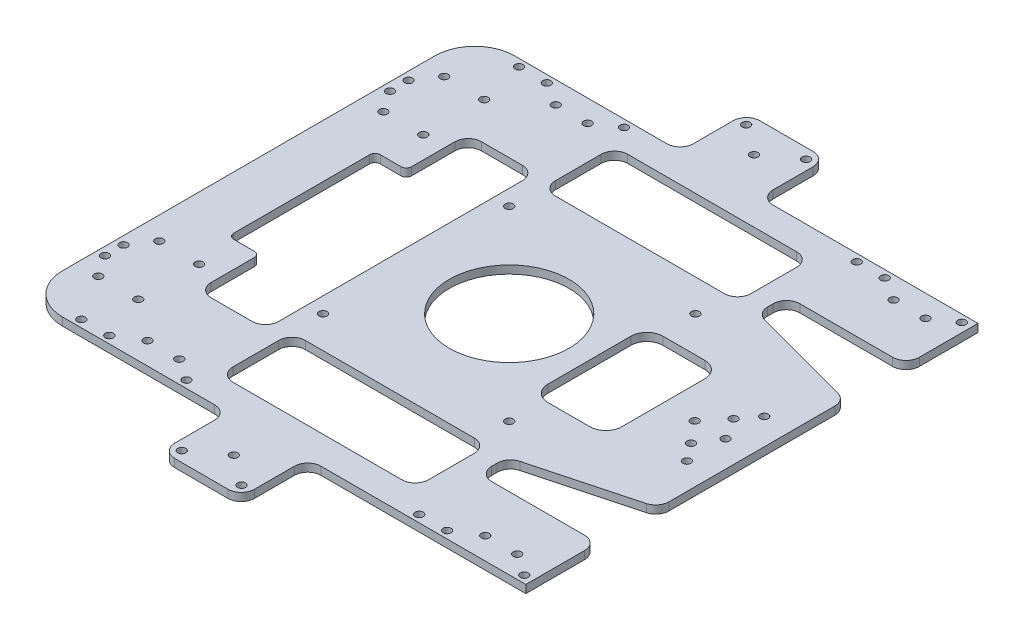
SolidWorks part; units mm, degrees
ref_plane "前视基准面" through (0, 0, 0) normal (0, 0, 1) x (1, 0, 0)
ref_plane "上视基准面" through (0, 0, 0) normal (0, 1, 0) x (1, 0, 0)
ref_plane "右视基准面" through (0, 0, 0) normal (1, 0, 0) x (0, 0, -1)
other "Configuration Table"
sketch "草图1" plane through (0, 0, 0) normal (0, 1, 0) x (1, 0, 0)
  line L0 (-91.25, 85) -> (-97.9595, 85)
  line L1 (-91.25, 85) -> (-35.75, 85)
  line L3 (-91.25, -85) -> (-35.75, -85)
  line L4 (91.25, 85) -> (91.25, 57.9182)
  line L5 (-91.25, 85) -> (91.25, -85) construction
  line L6 (-91.25, -85) -> (91.25, 85) construction
  line L7 (44.25, -85) -> (91.25, -85)
  line L8 (-97.9595, 85) -> (-97.9595, -85)
  line L9 (-82.75, -85) -> (-92.6165, -85) construction
  line L10 (-97.9595, -85) -> (-91.25, -85)
  line L11 (-89.4436, 33.7248) -> (-89.4436, 26.7248) construction
  line L13 (-74.4436, -42.1331) -> (-89.4436, -42.1331) construction
  line L14 (-89.4436, 85) -> (-89.4436, -85) construction
  line L15 (0, 0) -> (-228.1626, 0) construction
  line L23 (44.25, 85) -> (91.25, 85)
  line L24 (91.25, -57.9182) -> (91.25, -85)
  line L25 (46.356, 57.9182) -> (91.25, 57.9182)
  line L26 (46.356, 57.9182) -> (46.356, 47.0062)
  line L27 (46.356, -57.9182) -> (91.25, -57.9182)
  line L29 (-40.8461, 50.8132) -> (-66.2289, 50.8132)
  line L30 (-40.8461, 50.8132) -> (-40.8461, -50.8132)
  line L31 (-40.8461, -50.8132) -> (-66.2289, -50.8132)
  line L32 (-66.2289, 50.8132) -> (-66.2289, -50.8132)
  line L33 (0, 0) -> (0, -26.7248) construction
  line L34 (-35, 35) -> (35, 35) construction
  line L35 (-35, 35) -> (-35, -35) construction
  line L36 (-35, -35) -> (35, -35) construction
  line L37 (35, 35) -> (35, -35) construction
  line L38 (-35, 35) -> (35, -35) construction
  line L39 (-35, -35) -> (35, 35) construction
  line L40 (-35.75, -85) -> (-25.75, -85)
  line L41 (47.4478, 0) -> (171.4759, 0) construction
  line L42 (-20.75, -90) -> (-20.75, -104.9826)
  line L43 (-15.75, -109.9826) -> (4.25, -109.9826)
  line L44 (9.25, -104.9826) -> (9.25, -90)
  line L45 (14.25, -85) -> (44.25, -85)
  line L46 (14.25, 85) -> (44.25, 85)
  line L47 (9.25, 104.9826) -> (9.25, 90)
  line L48 (-15.75, 109.9826) -> (4.25, 109.9826)
  line L49 (-20.75, 90) -> (-20.75, 104.9826)
  line L50 (-35.75, 85) -> (-25.75, 85)
  line L51 (-34.6402, -47.0062) -> (38.8805, -47.0062)
  line L52 (-34.6402, 74.2132) -> (38.8805, 74.2132)
  line L53 (-34.6402, 74.2132) -> (-34.6402, 47.0062)
  line L54 (-34.6402, 47.0062) -> (38.8805, 47.0062)
  line L55 (38.8805, 74.2132) -> (38.8805, 47.0062)
  line L56 (38.8805, -74.2132) -> (38.8805, -47.0062)
  line L57 (-34.6402, -74.2132) -> (38.8805, -74.2132)
  line L58 (-34.6402, -74.2132) -> (-34.6402, -47.0062)
  line L59 (46.356, 47.0062) -> (91.25, 35)
  line L60 (91.25, 35) -> (91.25, -35)
  line L61 (91.25, -35) -> (46.356, -47.0062)
  line L62 (46.356, -47.0062) -> (46.356, -57.9182)
  line L63 (-89.4436, 65.0248) -> (-74.4436, 65.0248) construction
  line L64 (57.9405, 21.6087) -> (30.1732, 21.6087)
  line L65 (57.9405, 21.6087) -> (57.9405, -21.6087)
  line L66 (57.9405, -21.6087) -> (30.1732, -21.6087)
  line L67 (30.1732, 21.6087) -> (30.1732, -21.6087)
  line L68 (-74.4436, 65.0248) -> (-74.4436, 42.1331) construction
  line L69 (-74.4436, 42.1331) -> (-89.4436, 42.1331) construction
  line L70 (-89.4436, 42.1331) -> (-89.4436, 65.0248) construction
  line L71 (-89.4436, -42.1331) -> (-89.4436, -65.0248) construction
  line L72 (-74.4436, -65.0248) -> (-74.4436, -42.1331) construction
  line L73 (-89.4436, -65.0248) -> (-74.4436, -65.0248) construction
  circle A5 centre (-89.4436, 65.0248) radius 1.5
  circle A6 centre (-74.4436, 65.0248) radius 1.5
  circle A9 centre (-78.5908, -82.25) radius 1.5
  circle A10 centre (-68.0908, -82.25) radius 1.5
  circle A11 centre (-39.0908, -82.25) radius 1.5
  circle A12 centre (48.4092, -82.25) radius 1.5
  circle A13 centre (58.9092, -82.25) radius 1.5
  circle A14 centre (87.9092, -82.25) radius 1.5
  circle A15 centre (-78.5908, 82.25) radius 1.5
  circle A16 centre (-68.0908, 82.25) radius 1.5
  circle A17 centre (-39.0908, 82.25) radius 1.5
  circle A18 centre (48.4092, 82.25) radius 1.5
  circle A19 centre (58.9092, 82.25) radius 1.5
  circle A20 centre (87.9092, 82.25) radius 1.5
  circle A21 centre (-59.25, 76.75) radius 1.5
  circle A22 centre (-47.25, 76.75) radius 1.5
  circle A23 centre (-59.25, -76.75) radius 1.5
  circle A24 centre (-47.25, -76.75) radius 1.5
  circle A25 centre (67.75, 76.75) radius 1.5
  circle A26 centre (79.75, 76.75) radius 1.5
  circle A27 centre (67.75, -76.75) radius 1.5
  circle A28 centre (79.75, -76.75) radius 1.5
  circle A29 centre (-89.4436, 42.1331) radius 1.5
  circle A30 centre (-74.4436, 42.1331) radius 1.5
  circle A35 centre (-35, 35) radius 1.5
  circle A36 centre (-35, -35) radius 1.5
  circle A37 centre (35, -35) radius 1.5
  circle A38 centre (35, 35) radius 1.5
  arc A39 (-25.75, -85) -> (-20.75, -90) centre (-25.75, -90) cw
  arc A40 (4.25, -109.9826) -> (9.25, -104.9826) centre (4.25, -104.9826) ccw
  arc A41 (-20.75, -104.9826) -> (-15.75, -109.9826) centre (-15.75, -104.9826) ccw
  arc A42 (9.25, -90) -> (14.25, -85) centre (14.25, -90) cw
  circle A44 centre (-17, -106.1) radius 1.5
  circle A45 centre (5.5, -106.1) radius 1.5
  circle A46 centre (5.5, 106.1) radius 1.5
  circle A47 centre (-17, 106.1) radius 1.5
  arc A49 (9.25, 90) -> (14.25, 85) centre (14.25, 90) ccw
  arc A50 (-20.75, 104.9826) -> (-15.75, 109.9826) centre (-15.75, 104.9826) cw
  arc A51 (4.25, 109.9826) -> (9.25, 104.9826) centre (4.25, 104.9826) cw
  arc A52 (-25.75, 85) -> (-20.75, 90) centre (-25.75, 90) ccw
  circle A53 centre (0, 0) radius 22.5
  circle A54 centre (-74.4436, -42.1331) radius 1.5
  circle A55 centre (-89.4436, -42.1331) radius 1.5
  circle A56 centre (-74.4436, -65.0248) radius 1.5
  circle A57 centre (-89.4436, -65.0248) radius 1.5
  circle A58 centre (-5.75, -97.7894) radius 1.5
  circle A59 centre (-5.75, 97.7894) radius 1.5
  point P0 (0, 0)
  point P133 (-20.75, -85)
  point P139 (9.25, -85)
  point P167 (9.25, 85)
  point P168 (-20.75, 85)
  dimension "D3" = 70
  dimension "D4" = 70
  dimension "D5" = 3
  dimension "D7" = 3
  dimension "D8" = 3
  dimension "D10" = 5
  dimension "D11" = 5
  dimension "D1" = 170
  dimension "D2" = 182.5
  dimension "D6" = 7
  dimension "D9" = 15
  dimension "D12" = 22.8917
extrude "凸台-拉伸1" add sketch "草图1" along normal blind 3
fillet "圆角2" radius 15 1 edges at (-97.9595, 1.5, -85)
fillet "圆角3" radius 15 1 edges at (-97.9595, 1.5, 85)
sketch "草图2" plane through (0, 3, 0) normal (0, 1, 0) x (1, 0, 0)
  circle A0 centre (-94.8899, 57.079) radius 1.5
  circle A1 centre (-94.8899, 50.079) radius 1.5
  circle A2 centre (-94.8899, -50.079) radius 1.5
  circle A3 centre (-94.8899, -57.079) radius 1.5
extrude "切除-拉伸1" cut sketch "草图2" against normal through all
fillet "圆角6" radius 5 12 edges at (-40.8461, 1.5, 50.8132) (-66.2289, 1.5, 50.8132) (-66.2289, 1.5, -50.8132) (-40.8461, 1.5, -50.8132) (46.356, 1.5, -57.9182) (91.25, 1.5, -57.9182) (91.25, 1.5, 57.9182) (91.25, 1.5, -35) (91.25, 1.5, 35) (46.356, 1.5, -47.0062) (46.356, 1.5, 47.0062) (46.356, 1.5, 57.9182)
fillet "圆角7" radius 5 8 edges at (-34.6402, 1.5, -47.0062) (38.8805, 1.5, -47.0062) (38.8805, 1.5, -74.2132) (-34.6402, 1.5, -74.2132) (38.8805, 1.5, 74.2132) (-34.6402, 1.5, 74.2132) (38.8805, 1.5, 47.0062) (-34.6402, 1.5, 47.0062)
sketch "草图3" plane through (0, 3, 0) normal (0, 1, 0) x (1, 0, 0)
  line L0 (91.25, 0) -> (-155.3356, 0) construction
  line L1 (91.25, -31.1615) -> (91.25, 31.1615) construction
  circle A0 centre (81.3625, 14.5262) radius 1.5
  circle A1 centre (81.3625, -14.5262) radius 1.5
  circle A2 centre (76.3421, -7.9763) radius 1.5
  circle A3 centre (76.3421, 7.9763) radius 1.5
  circle A4 centre (81.3625, 0) radius 1.5
  circle A5 centre (69.7317, 0) radius 1.5
  dimension "D1" = 3
  dimension "D2" = 3
  dimension "D3" = 3
  dimension "D4" = 3
extrude "切除-拉伸2" cut sketch "草图3" against normal up to next
fillet "圆角8" radius 6 4 edges at (30.1732, 1.5, 21.6087) (57.9405, 1.5, 21.6087) (57.9405, 1.5, -21.6087) (30.1732, 1.5, -21.6087)
sketch "草图4" plane through (0, 3, 0) normal (0, 1, 0) x (1, 0, 0)
  line L0 (91.25, 0) -> (-164.2506, 0) construction
  line L1 (-78.0216, -27.5566) -> (-62.1048, -27.5566)
  line L2 (-78.0216, -27.5566) -> (-78.0216, 27.5566)
  line L3 (-78.0216, 27.5566) -> (-62.1048, 27.5566)
  line L4 (-62.1048, -27.5566) -> (-62.1048, 27.5566)
  line L5 (91.25, -31.1615) -> (91.25, 31.1615) construction
extrude "切除-拉伸3" cut sketch "草图4" against normal through all
fillet "圆角9" radius 2 2 edges at (-78.0216, 1.5, -27.5566) (-78.0216, 1.5, 27.5566)
fillet "圆角10" radius 2 2 edges at (-66.2289, 1.5, 27.5566) (-66.2289, 1.5, -27.5566)
